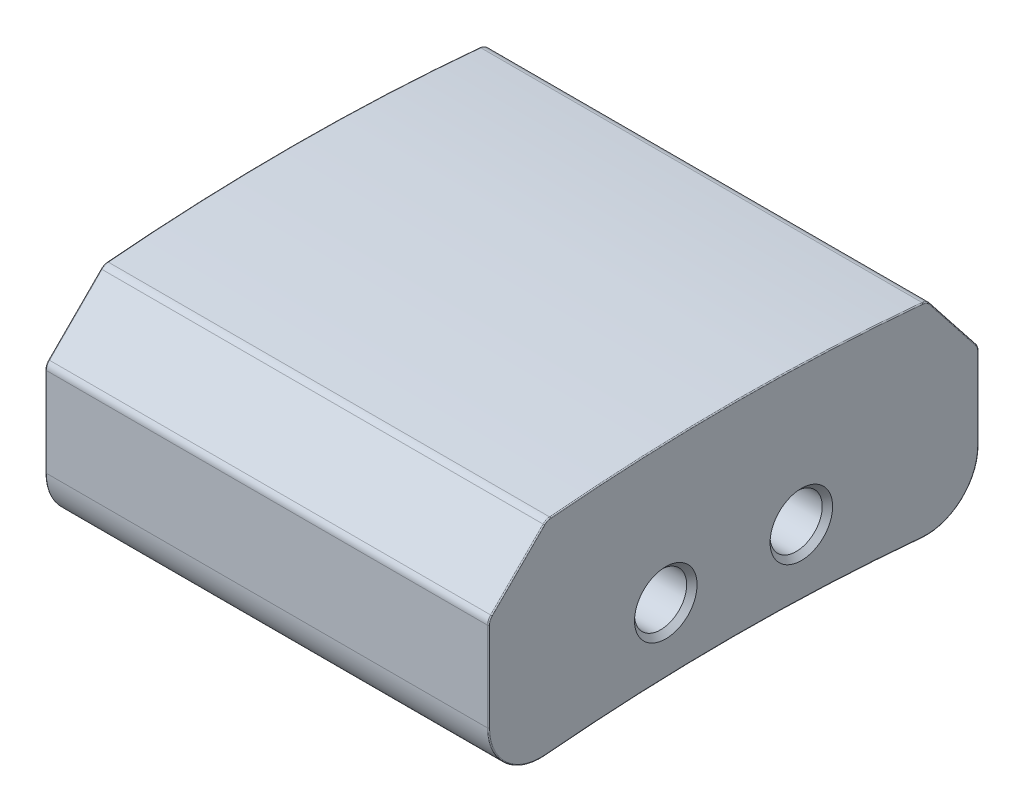
SolidWorks part; units mm, degrees
ref_plane "Front Plane" through (0, 0, 0) normal (0, 0, 1) x (1, 0, 0)
ref_plane "Top Plane" through (0, 0, 0) normal (0, 1, 0) x (1, 0, 0)
ref_plane "Right Plane" through (0, 0, 0) normal (1, 0, 0) x (0, 0, -1)
sketch "Sketch1" plane through (0, 0, 0) normal (0, 1, 0) x (1, 0, 0)
  line L0 (0, -55) -> (0, 55) construction
  line L1 (-4.25, 4.7) -> (4.25, 4.7)
  line L2 (-4.25, 4.7) -> (-4.25, -4.7)
  line L3 (-4.25, -4.7) -> (4.25, -4.7)
  line L4 (4.25, 4.7) -> (4.25, -4.7)
  line L5 (-55, 0) -> (55, 0) construction
  dimension "D1" = 8.5
  dimension "D2" = 4.25
  dimension "D3" = 9.4
  dimension "D4" = 4.7
extrude "Boss-Extrude1" add sketch "Sketch1" along normal blind 4.2
sketch "Sketch2" plane through (4.25, 0, 0) normal (1, 0, 0) x (0, 0, -1)
  line L0 (4.675, 0) -> (-4.675, 0) construction
  line L1 (-4.7, 4.2) -> (-4.7, 0) construction
  line L2 (4.7, 4.2) -> (4.7, 0) construction
  line L3 (-4.7, 4.2) -> (4.7, 4.2) construction
  line L4 (-4.7, 3.9) -> (-5.2535, 5.2417)
  line L5 (-5.2535, 5.2417) -> (3.8892, 7.1412)
  line L6 (3.8892, 7.1412) -> (5.6792, 5.0772)
  line L7 (5.6792, 5.0772) -> (4.7, 3.9)
  line L8 (4.7174, 0) -> (0, -2.9048)
  line L9 (0, -2.9048) -> (-4.7004, 0)
  arc A0 (-4.7004, 0) -> (4.7174, 0) centre (0.0085, -39.7219) cw
  arc A1 (-4.7, 3.9) -> (4.7, 3.9) centre (0, -35.8229) cw
  dimension "D3" = 40
  dimension "D4" = 40
  dimension "D1" = 0.3
  dimension "D2" = 0.3
extrude "Cut-Extrude1" cut sketch "Sketch2" against normal blind 14.2
chamfer "Chamfer1" distance 1 angle 45 2 edges at (0, 3.9, -4.7) (0, 3.9, 4.7) first distance on face at (0, 4.0385, 0) first distance on face at (0, 1.95, 4.7)
fillet "Fillet1" radius 1 2 edges at (0, 0, 4.7) (0, 0.0021, -4.7)
fillet "Fillet2" radius 0.2 4 edges at (0, 2.7579, -4.7) (0, 4.004, -3.7176) (0, 4.0162, 3.5838) (0, 2.9, 4.7)
fillet "Fillet3" radius 0.02 24 edges at (-4.25, 3.9885, -3.7091) (-4.25, 4.177, -0.0605) (-4.25, 4.0047, 3.5783) (-4.25, 3.4617, 4.1383) (-4.25, 2.8937, 4.6848) (-4.25, 1.9636, 4.7) (-4.25, 0.3717, 4.3744) (-4.25, 0.2781, -0.0002) (-4.25, 0.3734, -4.3745) (-4.25, 1.9001, -4.7) (-4.25, 2.7541, -4.689) (-4.25, 3.3744, -4.2139) (4.25, 0.3734, -4.3745) (4.25, 0.2781, -0.0002) (4.25, 0.3717, 4.3744) (4.25, 1.9636, 4.7) (4.25, 2.8937, 4.6848) (4.25, 3.4617, 4.1383) (4.25, 4.0047, 3.5783) (4.25, 4.177, -0.0605) (4.25, 3.9885, -3.7091) (4.25, 3.3744, -4.2139) (4.25, 2.7541, -4.689) (4.25, 1.9001, -4.7)
sketch "Sketch3" plane through (-4.25, 0, 0) normal (-1, 0, 0) x (0, 0, 1)
  line L0 (4.675, 0) -> (-4.675, 0) construction
  line L1 (0, -2.2369) -> (0, 2.2369) construction
  circle A0 centre (-1.3, 1.5) radius 0.5
  circle A1 centre (1.3, 1.5) radius 0.5
  dimension "D1" = 1
  dimension "D2" = 1
  dimension "D3" = 1.5
  dimension "D4" = 1.5
  dimension "D5" = 1.3
  dimension "D6" = 1.3
extrude "Cut-Extrude2" cut sketch "Sketch3" against normal blind 14.2
chamfer "Chamfer2" distance 0.1 angle 45 4 edges at (4.25, 1.5, -0.8) (4.25, 1.5, 1.8) (-4.25, 1.5, -0.8) (-4.25, 1.5, 1.8)
